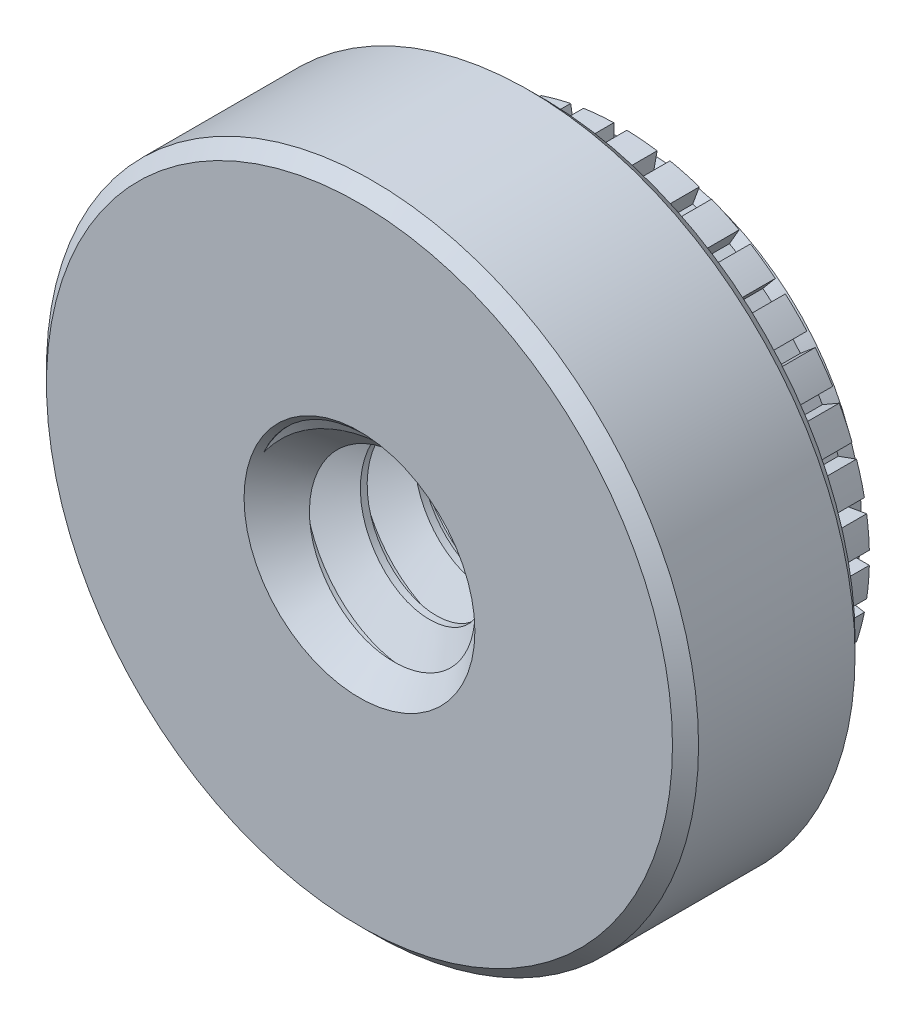
SolidWorks part; units mm, degrees
ref_plane "Front Plane" through (0, 0, 0) normal (0, 0, 1) x (1, 0, 0)
ref_plane "Top Plane" through (0, 0, 0) normal (0, 1, 0) x (1, 0, 0)
ref_plane "Right Plane" through (0, 0, 0) normal (1, 0, 0) x (0, 0, -1)
sketch "Sketch1" plane through (0, 0, 0) normal (0, 0, 1) x (1, 0, 0)
  circle A0 centre (0, 0) radius 3.175
  dimension "A" = 6.35
extrude "Extrude1" add sketch "Sketch1" against normal blind 1.778
sketch "Sketch15" plane through (0, 0, -1.778) normal (0, 0, -1) x (-1, 0, 0)
  circle A0 centre (0, 0) radius 2.1082
  dimension "hole dia" = 4.2164
sketch "Sketch2" plane through (0, 0, -1.778) normal (0, 0, -1) x (-1, 0, 0)
  circle A0 centre (0, 0) radius 2.4257
  dimension "D1" = 4.8514
extrude "Extrude2" add sketch "Sketch2" along normal blind 1.016
sketch "Sketch3" plane through (0, 0, -2.794) normal (0, 0, -1) x (-1, 0, 0)
  line L0 (0, 2.2352) -> (0, 3.175)
  circle A1 centre (0, 0) radius 3.175 construction
  circle A2 centre (0, 0) radius 2.2352
  circle A3 centre (0, 0) radius 2.2352 construction
  dimension "D1" = 0.1905
extrude "Cut-Extrude-Thin1" cut sketch "Sketch3" against normal up to surface (1.016 mm away) thin up to face at (3.175, 0, -1.778) thin type mid plane wall 0.127
pattern_circular "CirPattern1" count 36 over 360 about axis through (0, 0, -1.778) along (0, 0, 1) of "Cut-Extrude-Thin1"
sketch "Sketch5" plane through (0, 0, -2.794) normal (0, 0, -1) x (-1, 0, 0)
  circle A0 centre (0, 0) radius 3.175 construction
  circle A3 centre (0, 0) radius 2.0955
  dimension "C" = 4.191
extrude "Cut-Extrude1" cut sketch "Sketch5" against normal blind 0.254 draft 20 flip side to cut draft outward yes
chamfer "Chamfer2" distance 0.127 angle 45 2 edges at (3.175, 0, 0) (3.175, 0, -1.778)
sketch "Sketch7" plane through (0, 0, 0) normal (0, 0, 1) x (1, 0, 0)
  circle A0 centre (0, 0) radius 1.0732
  dimension "Thread Od" = 2.1463
extrude "Cut-Extrude3" cut sketch "Sketch7" against normal through all
sketch "Sketch8" plane through (0, 0, -2.794) normal (0, 0, -1) x (-1, 0, 0)
  circle A0 centre (0, 0) radius 1.0732 construction
  circle A1 centre (0, 0) radius 1.0732
curve "Helix/Spiral1" pitch 0.5292 height 5.969 radius 1.0732 centre (0, 0, -2.794) axis (0, 0, 1) start towards (0, 1, 0) parameters "pitch"=0.5292
sketch "Sketch9" plane through (0, 0, 0) normal (1, 0, 0) x (0, 0, -1)
  line L0 (3.257, 1.0732) -> (3.0586, 0.7294)
  line L1 (3.0586, 0.7294) -> (2.9924, 0.7294)
  line L2 (2.9924, 0.7294) -> (2.794, 1.0732)
  line L3 (3.257, 1.0732) -> (2.794, 1.0732)
  line L4 (3.0255, 1.0732) -> (3.0255, 0.7294) construction
  line L5 (3.1578, 0.9013) -> (2.8932, 0.9013) construction
  line L6 (2.794, -1.0732) -> (2.794, 1.0732) construction
  dimension "D1" = 60
  dimension "D2" = 0.0661
sweep "Sweep1" add profiles "Sketch9" path "Helix/Spiral1"
sketch "Sketch10" plane through (0, 0, 0) normal (0, 0, 1) x (1, 0, 0)
  circle A0 centre (0, 0) radius 3.175 construction
  circle A1 centre (0, 0) radius 3.175
extrude "Cut-Extrude4" cut sketch "Sketch10" along normal through all
sketch "Sketch11" plane through (0, 0, -2.794) normal (0, 0, -1) x (-1, 0, 0)
  circle A1 centre (0, 0) radius 2.0955 construction
  circle A2 centre (0, 0) radius 2.0955
extrude "Cut-Extrude5" cut sketch "Sketch11" along normal through all
sketch "Sketch13" plane through (0, 0, 0) normal (0, 0, 1) x (1, 0, 0)
  circle A2 centre (0, 0) radius 1.124
  circle A3 centre (0, 0) radius 1.124
  dimension "D1" = 0.0508
extrude "Cut-Extrude6" cut sketch "Sketch13" against normal through all draft 45
sketch "Sketch14" plane through (0, 0, -2.794) normal (0, 0, -1) x (-1, 0, 0)
  circle A2 centre (0, 0) radius 1.1367
  circle A3 centre (0, 0) radius 1.1367
  dimension "D1" = 0.0635
extrude "Cut-Extrude7" cut sketch "Sketch14" against normal through all draft 45
equation "\"D3@Helix/Spiral1\" = \"B@Extrude1\"+\"panel min.@Extrude2\"+.125"
equation "\"D2@Sketch9\" = \"pitch@Helix/Spiral1\"*.125"
equation "\"D3@Sketch9\" = \"pitch@Helix/Spiral1\"*.50"
equation "\"D1@Sketch2\" = \"hole dia@Sketch15\"+.025"
equation "\"D1@Cut-Extrude1\" = \"panel min.@Extrude2\"*.25"
